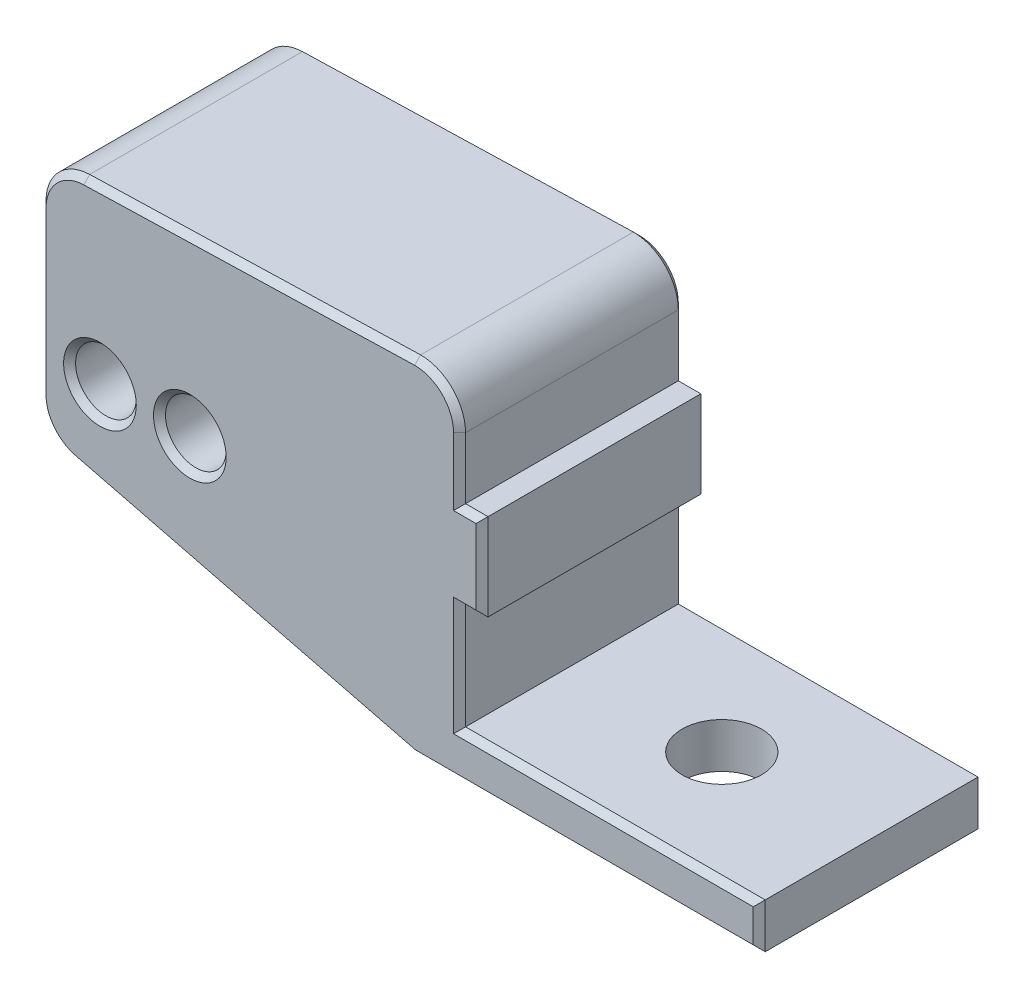
SolidWorks part; units mm, degrees
ref_plane "Front Plane" through (0, 0, 0) normal (0, 0, 1) x (1, 0, 0)
ref_plane "Top Plane" through (0, 0, 0) normal (0, 1, 0) x (1, 0, 0)
ref_plane "Right Plane" through (0, 0, 0) normal (1, 0, 0) x (0, 0, -1)
sketch "Sketch1" plane through (0, 0, 0) normal (0, 0, 1) x (1, 0, 0)
  line L0 (45.4899, -84.3159) -> (51.4899, -84.3159) construction
  line L1 (48.4899, -84.3159) -> (66.4899, -84.3159) construction
  line L2 (66.4899, -72.3159) -> (69.4899, -72.3159)
  line L3 (48.4899, -77.3159) -> (48.4899, -84.3159) construction
  line L4 (41.4899, -73.0103) -> (41.4899, -89.0659)
  line L7 (66.4899, -95.3159) -> (89.4899, -95.3159)
  line L9 (69.4899, -72.3159) -> (69.4899, -79.4159)
  line L10 (69.4899, -92.3159) -> (76.5899, -92.3159)
  line L11 (89.4899, -92.3159) -> (89.4899, -95.3159)
  line L12 (76.5899, -92.3159) -> (82.3899, -92.3159)
  line L14 (41.4899, -89.0659) -> (66.4899, -95.3159)
  line L17 (48.4899, -77.3159) -> (66.4899, -77.3159) construction
  line L18 (66.4899, -72.3159) -> (41.4899, -73.0103)
  line L19 (48.4899, -84.3159) -> (48.4899, -90.8159) construction
  line L20 (48.4899, -84.3159) -> (41.4899, -84.3159) construction
  line L21 (48.4899, -84.3159) -> (48.4899, -72.8159) construction
  line L22 (66.4899, -77.3159) -> (66.4899, -95.3159) construction
  line L23 (89.4899, 311.6195) -> (89.4899, -188.3805) construction
  line L29 (69.4899, -85.2159) -> (70.9899, -85.2159)
  line L31 (69.4899, -79.4159) -> (70.9899, -79.4159)
  line L32 (70.9899, -85.2159) -> (70.9899, -79.4159)
  line L33 (69.4899, -82.3159) -> (70.9899, -82.3159) construction
  line L34 (82.3899, -92.3159) -> (89.4899, -92.3159)
  line L35 (69.4899, -85.2159) -> (69.4899, -92.3159)
  circle A0 centre (48.4899, -77.3159) radius 3.025
  circle A1 centre (45.4899, -84.3159) radius 2.025
  circle A2 centre (51.4899, -84.3159) radius 2.025
  dimension "D3" = 4.05
  dimension "D4" = 6.05
  dimension "D1" = 3
  dimension "D2" = 6
  dimension "D5" = 6.5
  dimension "D6" = 7
  dimension "D7" = 11.5
  dimension "D8" = 23
  dimension "D9" = 25
  dimension "D10" = 20
  dimension "D11" = 20
  dimension "D12" = 8
  dimension "D13" = 5.8
extrude "Boss-Extrude1" add sketch "Sketch1" along normal blind 15
extrude "Boss-Extrude2" add sketch "Sketch1<2>" along normal up to surface (15 mm away) from offset 5.6 contours A0 region at (48.4899, -77.3159, 0) up to face at (47.5149, -84.3159, 15)
sketch "Sketch1<2>" plane through (0, 0, 0) normal (0, 0, 1) x (1, 0, 0) same geometry as "Sketch1"
sketch "Sketch2" plane through (0, -95.3159, 0) normal (0, -1, 0) x (1, 0, 0)
  line L0 (89.4899, 0) -> (69.4899, 15) construction
  line L1 (66.4899, 15) -> (89.4899, 15) construction
  line L2 (69.4899, 15) -> (89.4899, 15) construction
  circle A0 centre (79.4899, 7.5) radius 2.65
  dimension "D2" = 5.3
  dimension "D1" = 20
extrude "Cut-Extrude1" cut sketch "Sketch2" against normal blind 70
ref_plane "Plane1" through (0, 0, 25) normal (0, 0, 1) x (1, 0, 0)
fillet "Fillet1" radius 3 3 edges at (69.4899, -72.3159, 7.5) (41.4899, -73.0103, 7.5) (41.4899, -89.0659, 7.5)
chamfer "Chamfer1" distance 0.4 angle 45 33 edges at (53.5149, -84.3159, 0) (47.5149, -84.3159, 0) (51.5149, -77.3159, 0) (42.3394, -73.8365, 0) (41.4899, -81.3258, 0) (42.1253, -88.5698, 0) (55.1261, -92.4749, 0) (77.9899, -95.3159, 0) (89.4899, -93.8159, 0) (79.4899, -92.3159, 0) (69.4899, -88.7659, 0) (70.2399, -85.2159, 0) (70.9899, -82.3159, 0) (70.2399, -79.4159, 0) (69.4899, -77.3659, 0) (68.6112, -73.1945, 0) (55.4483, -72.6226, 0) (53.5149, -84.3159, 15) (70.2399, -79.4159, 15) (70.9899, -82.3159, 15) (70.2399, -85.2159, 15) (69.4899, -88.7659, 15) (79.4899, -92.3159, 15) (89.4899, -93.8159, 15) (77.9899, -95.3159, 15) (55.1261, -92.4749, 15) (42.1253, -88.5698, 15) (41.4899, -81.3258, 15) (42.3394, -73.8365, 15) (55.4483, -72.6226, 15) (68.6112, -73.1945, 15) (69.4899, -77.3659, 15) (47.5149, -84.3159, 15)
